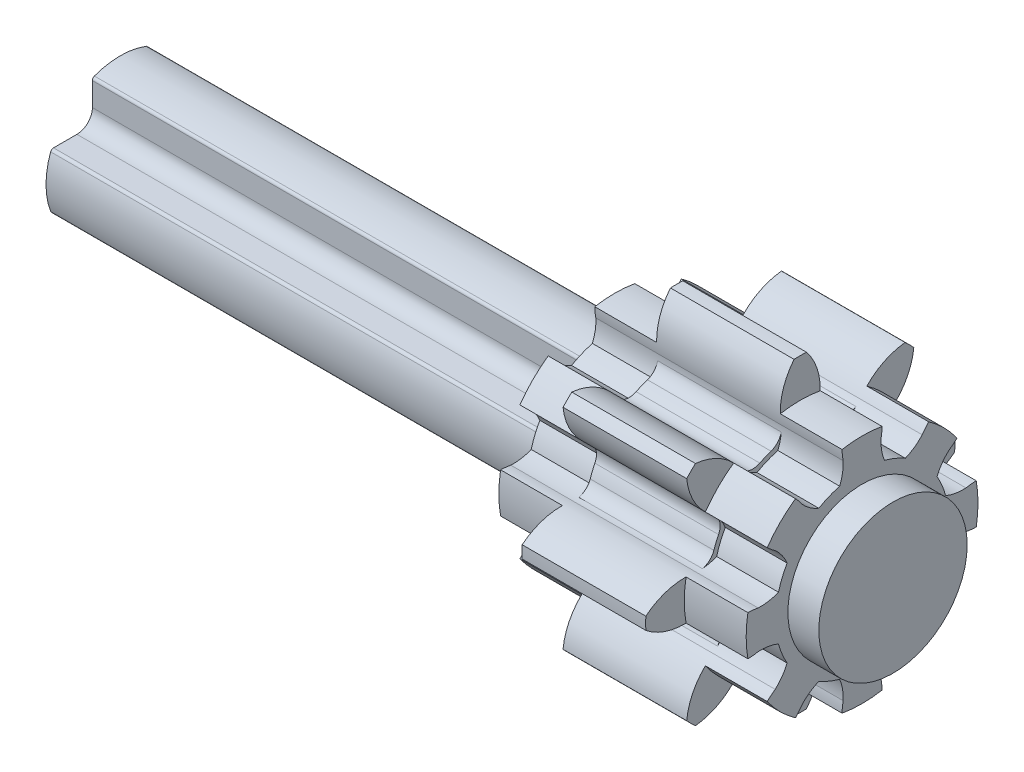
SolidWorks part; units mm, degrees
material "PET"
ref_plane "Alzado" through (0, 0, 0) normal (0, 0, 1) x (1, 0, 0)
ref_plane "Planta" through (0, 0, 0) normal (0, 1, 0) x (1, 0, 0)
ref_plane "Vista lateral" through (0, 0, 0) normal (1, 0, 0) x (0, 0, -1)
sketch "Croquis1" plane through (0, 0, 0) normal (1, 0, 0) x (0, 0, -1)
  circle A1 centre (0, 0) radius 2.8
  line B0 (-1.4, 0.9) -> (-2.1564, 0.9)
  line B1 (0.9, -2.1564) -> (0.9, -1.4)
  line B2 (-0.9, -2.1564) -> (-0.9, -1.4)
  line B3 (2.1564, 0.9) -> (1.4, 0.9)
  line B4 (2.1564, -0.9) -> (1.4, -0.9)
  line B5 (-0.9, 1.4) -> (-0.9, 2.1564)
  line B6 (0.9, 1.4) -> (0.9, 2.1564)
  line B7 (-1.4, -0.9) -> (-2.1564, -0.9)
  arc B8 (-2.2501, 0.8348) -> (-2.2501, -0.8348) centre (0, 0) ccw
  arc B9 (-1.4, -0.9) -> (-0.9, -1.4) centre (-1.4, -1.4) cw
  arc B10 (0.9, -1.4) -> (1.4, -0.9) centre (1.4, -1.4) cw
  arc B11 (1.4, 0.9) -> (0.9, 1.4) centre (1.4, 1.4) cw
  arc B12 (-0.9, 1.4) -> (-1.4, 0.9) centre (-1.4, 1.4) cw
  arc B13 (0.8348, 2.2501) -> (-0.8348, 2.2501) centre (0, 0) ccw
  arc B14 (2.2501, -0.8348) -> (2.2501, 0.8348) centre (0, 0) ccw
  arc B15 (-0.8348, -2.2501) -> (0.8348, -2.2501) centre (0, 0) ccw
  arc B16 (-0.8348, 2.2501) -> (-0.9, 2.1564) centre (-0.8, 2.1564) ccw
  arc B17 (0.8348, 2.2501) -> (0.9, 2.1564) centre (0.8, 2.1564) cw
  arc B18 (2.2501, 0.8348) -> (2.1564, 0.9) centre (2.1564, 0.8) ccw
  arc B19 (2.2501, -0.8348) -> (2.1564, -0.9) centre (2.1564, -0.8) cw
  arc B20 (0.9, -2.1564) -> (0.8348, -2.2501) centre (0.8, -2.1564) cw
  arc B21 (-0.8348, -2.2501) -> (-0.9, -2.1564) centre (-0.8, -2.1564) cw
  arc B22 (-2.1564, -0.9) -> (-2.2501, -0.8348) centre (-2.1564, -0.8) cw
  arc B23 (-2.1564, 0.9) -> (-2.2501, 0.8348) centre (-2.1564, 0.8) ccw
  dimension "D1" = 5.6
sketch_block_instance "Axle Section Block Rounded 0.1 mm-1"
sketch_block "Axle Section Block Rounded 0.1 mm" parameters "D1"=4.8, "D3"=0.5, "D4"=0.1, "D2"=1.8
extrude "Saliente-Extruir1" add sketch "Croquis1" along normal mid plane 8
sketch "Croquis2" plane through (0, 0, 0) normal (1, 0, 0) x (0, 0, -1)
  circle A0 centre (0, 0) radius 2.95
  circle A1 centre (0, 0) radius 2.8 construction
  circle A2 centre (0, 0) radius 2.8
  dimension "D1" = 5.9
extrude "Saliente-Extruir2" add sketch "Croquis2" along normal mid plane 4
sketch "Profile" plane through (0, 0, 0) normal (1, 0, 0) x (0, 0, -1)
  line L0 (0, 0) -> (0, 5) construction
  line L1 (-0.2, 4.996) -> (-0.8, 2.6833) construction
  arc A0 (0.2, 4.996) -> (-0.2, 4.996) centre (0, 0) ccw
  arc A1 (0.2, 4.996) -> (0.4, 2.7713) centre (-1.3524, 3.7351) cw
  arc A2 (0.8, 2.6833) -> (-0.8, 2.6833) centre (0, 0) ccw construction
  arc A3 (-0.2, 4.996) -> (-0.4, 2.7713) centre (1.3524, 3.7351) ccw
  arc A4 (0.4, 2.7713) -> (-0.4, 2.7713) centre (0, 0) ccw
  dimension "D1" = 10
  dimension "D4" = 5.6
  dimension "D5" = 2
  dimension "D6" = 0.4
  dimension "D2" = 0.2
  dimension "D3" = 0.8
extrude "Tooth" add sketch "Profile" along normal mid plane 4
fillet "Redondeo1" radius 0.5 2 edges at (0, 2.9122, -0.4704) (0, 2.9122, 0.4704)
pattern_circular "Matriz Teeth" count 8 over 360 about axis through (4, 0, 0) along (-1, 0, 0) of "Tooth", "Redondeo1"
sketch "Croquis3" plane through (4, 0, 0) normal (1, 0, 0) x (0, 0, -1)
  circle A0 centre (0, 0) radius 2.4
  arc A1 (2.2501, -0.8348) -> (2.2501, 0.8348) centre (0, 0) ccw construction
extrude "Cortar-Extruir1" cut sketch "Croquis3" against normal blind 0.2
sketch "Croquis4" plane through (-4, 0, 0) normal (-1, 0, 0) x (0, 0, 1)
  circle A0 centre (0, 0) radius 2.4
  arc A1 (0.8348, 2.2501) -> (-0.8348, 2.2501) centre (0, 0) ccw construction
extrude "Cortar-Extruir2" cut sketch "Croquis4" against normal blind 0.2
sketch "Sketch1" plane through (0, 0, 0) normal (1, 0, 0) x (0, 0, -1)
  line L0 (-0.7247, 2.7046) -> (-0.6988, 2.608)
  line L2 (0.6988, 2.608) -> (0.7247, 2.7046)
  line L3 (0, 2.7) -> (0, 0) construction
  line L4 (-0.7247, 2.7046) -> (0.7247, 2.7046) construction
  arc A0 (0.6988, 2.608) -> (-0.6988, 2.608) centre (0, 0) ccw
  arc A1 (-0.6471, 3.6937) -> (0.6471, 3.6937) centre (0, 0) cw
  arc A2 (-0.2, 4.996) -> (-0.6124, 3.362) centre (1.3524, 3.7351) ccw construction
  arc A3 (0.6124, 3.362) -> (0.2, 4.996) centre (-1.3524, 3.7351) ccw construction
  arc A4 (-0.6471, 3.6937) -> (-0.6124, 3.362) centre (1.3524, 3.7351) ccw
  arc A5 (0.6471, 3.6937) -> (0.6124, 3.362) centre (-1.3524, 3.7351) cw
  arc A6 (-0.6124, 3.362) -> (-0.7247, 2.7046) centre (-2.1102, 3.2794) cw
  arc A7 (0.6124, 3.362) -> (0.7247, 2.7046) centre (2.1102, 3.2794) ccw
  arc A8 (-0.7247, 2.7046) -> (0.7247, 2.7046) centre (0, 0) cw construction
  dimension "D1" = 3.75
  dimension "D3" = 2.7
  dimension "D4" = 1.5
  dimension "D5" = 2.8
  dimension "D2" = 30
extrude "Boss-Extrude1" add sketch "Sketch1" along normal up to surface and the other way up to surface up to face at (4, 0, -2.4) other way up to face at (-4, 0, -2.8)
ref_axis "Axis1" through (4.4, 0, 0) along (-1, 0, 0)
pattern_circular "CirPattern1" count 8 over 360 about axis through (4.4, 0, 0) along (-1, 0, 0) of "Boss-Extrude1"
sketch "Sketch2" plane through (0, 0, 0) normal (1, 0, 0) x (0, 0, -1)
  circle A0 centre (0, 0) radius 2.4
extrude "Boss-Extrude2" add sketch "Sketch2" along normal blind 5
sketch "Sketch3" plane through (0, 0, 0) normal (-1, 0, 0) x (0, 0, 1)
  line L8 (-0.9, 2.1564) -> (-0.9, 1.4)
  line L9 (-1.4, 0.9) -> (-2.1564, 0.9)
  line L10 (-2.1564, -0.9) -> (-1.4, -0.9)
  line L11 (-0.9, -1.4) -> (-0.9, -2.1564)
  line L12 (0.9, -2.1564) -> (0.9, -1.4)
  line L13 (1.4, -0.9) -> (2.1564, -0.9)
  line L14 (2.1564, 0.9) -> (1.4, 0.9)
  line L15 (0.9, 1.4) -> (0.9, 2.1564)
  line L16 (-0.9, 2.1564) -> (-0.9, 1.4)
  line L17 (-1.4, 0.9) -> (-2.1564, 0.9)
  line L18 (-2.1564, -0.9) -> (-1.4, -0.9)
  line L19 (-0.9, -1.4) -> (-0.9, -2.1564)
  line L20 (0.9, -2.1564) -> (0.9, -1.4)
  line L21 (1.4, -0.9) -> (2.1564, -0.9)
  line L22 (2.1564, 0.9) -> (1.4, 0.9)
  line L23 (0.9, 1.4) -> (0.9, 2.1564)
  arc A16 (0.9, 2.1564) -> (0.8348, 2.2501) centre (0.8, 2.1564) ccw
  arc A17 (0.8348, 2.2501) -> (-0.8348, 2.2501) centre (0, 0) ccw
  arc A18 (-0.8348, 2.2501) -> (-0.9, 2.1564) centre (-0.8, 2.1564) ccw
  arc A19 (-1.4, 0.9) -> (-0.9, 1.4) centre (-1.4, 1.4) ccw
  arc A20 (-2.1564, 0.9) -> (-2.2501, 0.8348) centre (-2.1564, 0.8) ccw
  arc A21 (-2.2501, 0.8348) -> (-2.2501, -0.8348) centre (0, 0) ccw
  arc A22 (-2.2501, -0.8348) -> (-2.1564, -0.9) centre (-2.1564, -0.8) ccw
  arc A23 (-0.9, -1.4) -> (-1.4, -0.9) centre (-1.4, -1.4) ccw
  arc A24 (-0.9, -2.1564) -> (-0.8348, -2.2501) centre (-0.8, -2.1564) ccw
  arc A25 (-0.8348, -2.2501) -> (0.8348, -2.2501) centre (0, 0) ccw
  arc A26 (0.8348, -2.2501) -> (0.9, -2.1564) centre (0.8, -2.1564) ccw
  arc A27 (1.4, -0.9) -> (0.9, -1.4) centre (1.4, -1.4) ccw
  arc A28 (2.1564, -0.9) -> (2.2501, -0.8348) centre (2.1564, -0.8) ccw
  arc A29 (2.2501, -0.8348) -> (2.2501, 0.8348) centre (0, 0) ccw
  arc A30 (2.2501, 0.8348) -> (2.1564, 0.9) centre (2.1564, 0.8) ccw
  arc A31 (0.9, 1.4) -> (1.4, 0.9) centre (1.4, 1.4) ccw
  arc A32 (0.9, 2.1564) -> (0.8348, 2.2501) centre (0.8, 2.1564) ccw
  arc A33 (0.8348, 2.2501) -> (-0.8348, 2.2501) centre (0, 0) ccw
  arc A34 (-0.8348, 2.2501) -> (-0.9, 2.1564) centre (-0.8, 2.1564) ccw
  arc A35 (-1.4, 0.9) -> (-0.9, 1.4) centre (-1.4, 1.4) ccw
  arc A36 (-2.1564, 0.9) -> (-2.2501, 0.8348) centre (-2.1564, 0.8) ccw
  arc A37 (-2.2501, 0.8348) -> (-2.2501, -0.8348) centre (0, 0) ccw
  arc A38 (-2.2501, -0.8348) -> (-2.1564, -0.9) centre (-2.1564, -0.8) ccw
  arc A39 (-0.9, -1.4) -> (-1.4, -0.9) centre (-1.4, -1.4) ccw
  arc A40 (-0.9, -2.1564) -> (-0.8348, -2.2501) centre (-0.8, -2.1564) ccw
  arc A41 (-0.8348, -2.2501) -> (0.8348, -2.2501) centre (0, 0) ccw
  arc A42 (0.8348, -2.2501) -> (0.9, -2.1564) centre (0.8, -2.1564) ccw
  arc A43 (1.4, -0.9) -> (0.9, -1.4) centre (1.4, -1.4) ccw
  arc A44 (2.1564, -0.9) -> (2.2501, -0.8348) centre (2.1564, -0.8) ccw
  arc A45 (2.2501, -0.8348) -> (2.2501, 0.8348) centre (0, 0) ccw
  arc A46 (2.2501, 0.8348) -> (2.1564, 0.9) centre (2.1564, 0.8) ccw
  arc A47 (0.9, 1.4) -> (1.4, 0.9) centre (1.4, 1.4) ccw
  dimension "D1" = 0
extrude "Boss-Extrude3" add sketch "Sketch3" along normal offset from surface (20 mm away) 25 up to face at (5, 0, -2.4)
